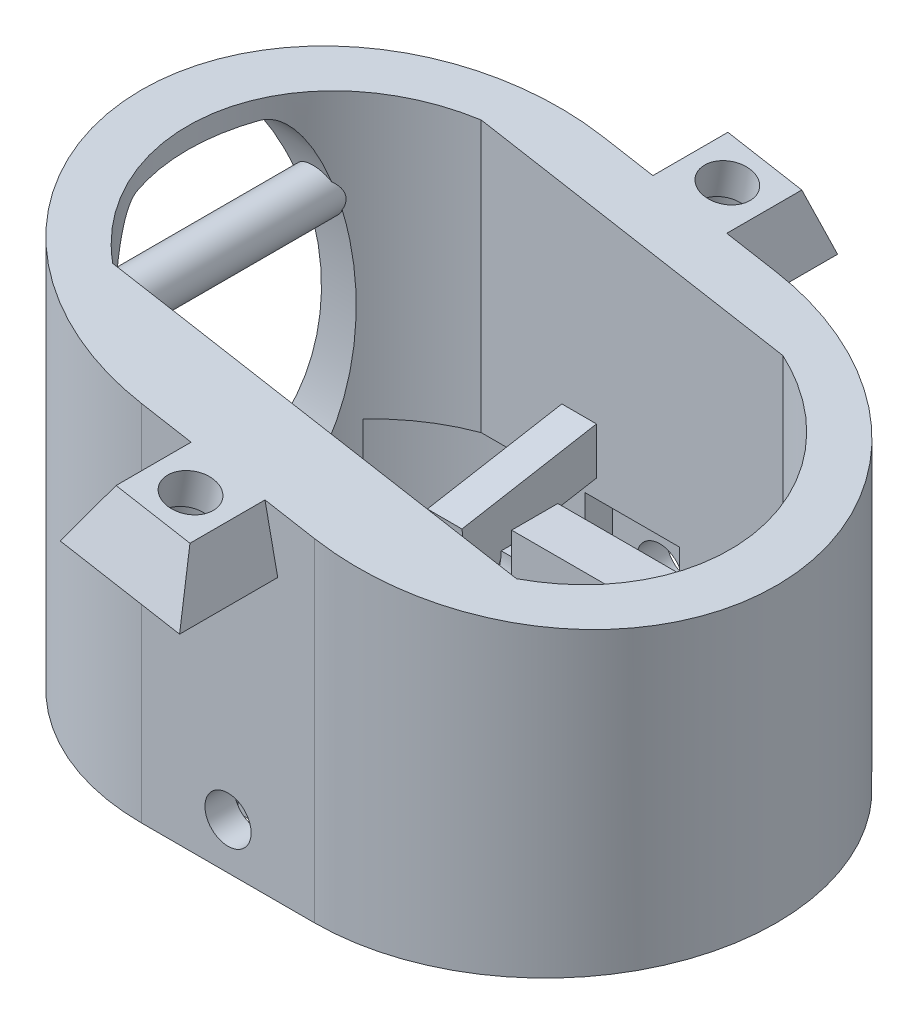
SolidWorks part; units mm, degrees
ref_plane "Front Plane" through (0, 0, 0) normal (0, 0, 1) x (1, 0, 0)
ref_plane "Top Plane" through (0, 0, 0) normal (0, 1, 0) x (1, 0, 0)
ref_plane "Right Plane" through (0, 0, 0) normal (1, 0, 0) x (0, 0, -1)
sketch "Sketch1" plane through (0, 0, 0) normal (0, 1, 0) x (1, 0, 0)
  line L0 (-7.5, 0) -> (7.5, 0) construction
  line L1 (-7.5, 20) -> (7.5, 20)
  line L2 (-7.5, -20) -> (7.5, -20)
  line L3 (22.4666, 10) -> (22.4666, -10) construction
  line L4 (22.4666, 10) -> (20.8037, 8.8889) construction
  line L5 (17.4875, -12.5) -> (-15.6093, -12.5)
  line L6 (22.4666, 10) -> (24.1296, 11.1111) construction
  line L7 (-7.5, 15) -> (13.0678, 15)
  line L8 (-7.5, 16) -> (7.5, 16) construction
  line L9 (-7.5, -16) -> (7.5, -16) construction
  line L10 (20.2481, 9.7204) -> (21.3592, 8.0574) construction
  line L11 (22.4666, -10) -> (20.8037, -8.8889) construction
  line L12 (22.4666, -10) -> (24.1296, -11.1111) construction
  line L13 (20.2481, -9.7204) -> (21.3592, -8.0574) construction
  line L14 (22.4666, 0) -> (23.5, 0) construction
  line L15 (0, 0) -> (0, -20) construction
  line L16 (-7.5, 17.1) -> (-7.5, 14.9)
  line L17 (0, -17.45) -> (4.1, -20) construction
  line L18 (-4.1, -15.05) -> (4.1, -15.05)
  line L19 (-4.1, -15.05) -> (-4.1, -17.45)
  line L20 (-7.5, -14.9) -> (-7.5, -17.1)
  line L21 (-4.1, -17.45) -> (4.1, -17.45)
  line L22 (4.1, -15.05) -> (4.1, -17.45)
  line L23 (-4.1, 17.4) -> (4.1, 17.4)
  line L24 (-4.1, 17.4) -> (-4.1, 15)
  line L25 (-4.1, 15) -> (4.1, 15)
  line L26 (4.1, 17.4) -> (4.1, 15)
  line L27 (4.1, -20) -> (4.1, -12.5) construction
  line L28 (4.1, -12.5) -> (0, -15.05) construction
  line L29 (-18.3972, 10.1618) -> (-20.0061, 11.6622)
  line L31 (-20.0061, -11.6622) -> (-18.3972, -10.1618)
  arc A0 (-7.5, 20) -> (-7.5, -20) centre (-7.5, 0) ccw
  arc A1 (7.5, -20) -> (7.5, 20) centre (7.5, 0) ccw
  arc A2 (17.4875, -12.5) -> (13.0678, 15) centre (7.5, 0) ccw
  arc A3 (-18.3972, -10.1618) -> (-7.5, -14.9) centre (-7.5, 0) ccw
  arc A4 (-7.5, 16) -> (-7.5, -16) centre (-7.5, 0) ccw construction
  arc A5 (7.5, -16) -> (7.5, 16) centre (7.5, 0) ccw construction
  circle A6 centre (22.4666, 10) radius 1.1
  circle A7 centre (22.4666, -10) radius 1.1
  arc A8 (-7.5, 17.1) -> (-20.0061, 11.6622) centre (-7.5, 0) ccw
  arc A9 (-7.5, 14.9) -> (-18.3972, 10.1618) centre (-7.5, 0) ccw
  arc A10 (-7.5, 17.1) -> (-20.0061, 11.6622) centre (-7.5, 0) ccw
  arc A11 (-20.0061, -11.6622) -> (-7.5, -17.1) centre (-7.5, 0) ccw
  arc A12 (-20.0061, -11.6622) -> (-7.5, -17.1) centre (-7.5, 0) ccw
  arc A13 (-19.2017, -10.912) -> (-19.2017, 10.912) centre (-7.5, 0) cw
  point P3 (0, 0)
  point P23 (20.8037, 8.8889)
  point P31 (20.8037, -8.8889)
  point P32 (0, -20)
  point P48 (0, -15.05)
  point P54 (4.1, -16.25)
  point P55 (4.1, -16.25)
  dimension "D7" = 2.2
  dimension "D10" = 34.2
  dimension "D11" = 29.8
  dimension "D14" = 4
  dimension "D1" = 15
  dimension "D2" = 40
  dimension "D3" = 7.5
  dimension "D4" = 5
  dimension "D6" = 20
  dimension "D8" = 8.2
  dimension "D9" = 2.4
  dimension "D12" = 137
  dimension "D13" = 137
  dimension "D5" = 4
extrude "Boss-Extrude1" add sketch "Sketch1" along normal blind 10 and the other way blind 10 contours L2 A1 L1 A0 A7 A6 L16 A9 L7 A2 L5 L18 L20 A8 region at (0, 0, -19.3199)
sketch "Sketch3" plane through (0, 10, 0) normal (0, 1, 0) x (1, 0, 0)
  line L0 (-7.5, 0) -> (7.5, 0) construction
  line L1 (-7.5, 20) -> (7.5, 20)
  line L2 (-7.5, -20) -> (7.5, -20)
  line L3 (-7.5, 20) -> (7.5, 20) construction
  line L6 (13.0678, 15) -> (-13.0678, 15)
  line L8 (17.4875, -12.5) -> (-17.4875, -12.5)
  line L11 (-7.5, 15) -> (-4.1, 15) construction
  line L12 (-7.5, 16) -> (7.5, 16) construction
  line L13 (-7.5, -16) -> (7.5, -16) construction
  arc A0 (-7.5, 20) -> (-7.5, -20) centre (-7.5, 0) ccw
  arc A1 (7.5, -20) -> (7.5, 20) centre (7.5, 0) ccw
  arc A2 (-7.5, 20) -> (-7.5, -20) centre (-7.5, 0) ccw construction
  arc A3 (17.4875, -12.5) -> (13.0678, 15) centre (7.5, 0) ccw
  arc A4 (-13.0678, 15) -> (-17.4875, -12.5) centre (-7.5, 0) ccw
  arc A5 (-7.5, 16) -> (-7.5, -16) centre (-7.5, 0) ccw construction
  arc A6 (7.5, -16) -> (7.5, 16) centre (7.5, 0) ccw construction
  point P2 (0, 0)
  dimension "D2" = 7.5
  dimension "D1" = 4
extrude "Boss-Extrude2" add sketch "Sketch3" against normal blind 11
sketch "Sketch4" plane through (0, 0, 0) normal (0, 0, 1) x (1, 0, 0)
  line L0 (-7.5, -10) -> (7.5, -10) construction
  line L1 (-4, -2) -> (4, -2) construction
  line L2 (-4, -2) -> (-4, -10) construction
  line L3 (-4, -10) -> (4, -10) construction
  line L4 (4, -2) -> (4, -10) construction
  line L5 (0, 0) -> (0, -2) construction
  line L6 (-4, -10) -> (4, -2) construction
  circle A0 centre (0, -6) radius 2
  point P11 (0, -6)
  dimension "D2" = 4
  dimension "D1" = 8
extrude "Cut-Extrude1" cut sketch "Sketch4" against normal blind 25 and the other way blind 35
sketch "Sketch5" plane through (0, 10, 0) normal (0, 1, 0) x (1, 0, 0)
  line L0 (-7.5, 0) -> (7.5, 0) construction
  line L1 (-7.5, 20) -> (7.5, 20)
  line L2 (-7.5, -20) -> (7.5, -20)
  line L3 (-7.5, 20) -> (7.5, 20) construction
  line L6 (-13.0678, 15) -> (13.0678, 15)
  line L8 (17.4875, -12.5) -> (-17.4875, -12.5)
  line L10 (-7.5, 16) -> (7.5, 16) construction
  line L11 (-7.5, -16) -> (7.5, -16) construction
  arc A0 (-7.5, 20) -> (-7.5, -20) centre (-7.5, 0) ccw
  arc A1 (7.5, -20) -> (7.5, 20) centre (7.5, 0) ccw
  arc A2 (17.4875, -12.5) -> (13.0678, 15) centre (7.5, 0) ccw
  arc A3 (-13.0678, 15) -> (-17.4875, -12.5) centre (-7.5, 0) ccw
  arc A4 (-7.5, 16) -> (-7.5, -16) centre (-7.5, 0) ccw construction
  arc A5 (7.5, -16) -> (7.5, 16) centre (7.5, 0) ccw construction
  point P2 (0, 0)
  point P22 (0, -12.5)
  dimension "D1" = 7.5
extrude "Boss-Extrude3" add sketch "Sketch5" along normal blind 15
sketch "Sketch6" plane through (0, 0, 0) normal (0, 0, 1) x (1, 0, 0)
  line L0 (-27.5, 25) -> (27.5, 15.302)
  line L1 (27.5, -10) -> (27.5, 25) construction
  line L2 (-7.5, 25) -> (-27.5, 25) construction
  line L3 (-27.5, 25) -> (27.5, 25)
  line L4 (27.5, 25) -> (27.5, 15.302)
  dimension "D1" = 10
extrude "Cut-Extrude2" cut sketch "Sketch6" against normal blind 20 and the other way blind 20
sketch "Sketch7" plane through (0, 0, 0) normal (0, 0, 1) x (1, 0, 0)
  line L0 (-27.5, 25) -> (-27.5, -10) construction
  line L1 (-27.5, -10) -> (-7.5, -10) construction
  line L2 (-22.5, 24.1184) -> (-22.5, -10) construction
  line L3 (-7.5, -10) -> (-7.5, 21.4735) construction
  line L4 (-13.0678, 22.4552) -> (-23.5, 24.2947) construction
  line L5 (-27.5, 25) -> (-27.5, -10)
  arc A0 (-26.7857, -7.5) -> (-26.7857, 22.5) centre (-50.8929, 7.5) ccw
  arc A1 (-26.7857, -7.5) -> (-27.5, -10) centre (-22.7679, -10) ccw
  arc A2 (-27.5, 25) -> (-26.7857, 22.5) centre (-22.7679, 25) ccw
  point P0 (-27.5, 25)
  dimension "D1" = 2.5
  dimension "D2" = 5
extrude "Cut-Extrude3" cut sketch "Sketch7" against normal blind 20 and the other way blind 20
sketch "Sketch8" plane through (0, 0, 0) normal (1, 0, 0) x (0, 0, -1)
  line L0 (0, 7.5) -> (0, 0) construction
  line L1 (5.2973, 22.5) -> (-5.2973, 22.5)
  line L2 (10.5946, 7.5) -> (-10.5946, 7.5) construction
  line L3 (5.2973, -7.5) -> (-5.2973, -7.5)
  ellipse E0 centre (5.2973, 7.5) end of major axis (5.2973, 22.5) minor radius 5.2973 (5.2973, -7.5) -> (5.2973, 22.5) ccw
  ellipse E1 centre (-5.2973, 7.5) end of major axis (-5.2973, 22.5) minor radius 5.2973 (-5.2973, 22.5) -> (-5.2973, -7.5) ccw
  dimension "D1" = 30
  dimension "D2" = 21.1891
extrude "Cut-Extrude4" cut sketch "Sketch8" against normal blind 40
sketch "Sketch9" plane through (0, 0, 0) normal (0, 0, 1) x (1, 0, 0)
  line L0 (-24.6917, 22.5) -> (-21.8926, 15.5419) construction
  line L1 (-26.7857, 22.5) -> (-22.5976, 22.5) construction
  line L2 (-23.5325, 15.0872) -> (-21.8926, 15.5419) construction
  line L3 (-21.8926, 15.5419) -> (-20.2527, 15.9967) construction
  line L4 (-23.9221, 16.4923) -> (-23.1428, 13.682) construction
  circle A0 centre (-21.8926, 15.5419) radius 2
  arc A2 (-26.1088, -6.3529) -> (-26.1088, 21.3529) centre (-50.8929, 7.5) ccw construction
  spline S1 degree 3 poles (-22.5976, -7.5) (-22.5373, -7.5) (-22.4754, -7.4764) (-22.3489, -7.3888) (-22.284, -7.3239) (-22.1573, -7.1668) (-22.0949, -7.0742) (-21.9716, -6.8671) (-21.9106, -6.7525) (-21.734, -6.3915) (-21.6227, -6.1255) (-21.409, -5.561) (-21.3068, -5.2623) (-21.0161, -4.3444) (-20.8408, -3.6968) (-20.5233, -2.3725) (-20.3809, -1.6929) (-20.128, -0.3198) (-20.0173, 0.3753) (-19.8265, 1.7801) (-19.7466, 2.4892) (-19.5546, 4.6227) (-19.4899, 6.0612) (-19.4897, 8.9332) (-19.5543, 10.3716) (-19.746, 12.5054) (-19.8259, 13.2147) (-20.0165, 14.6196) (-20.1273, 15.3155) (-20.3806, 16.6918) (-20.5227, 17.3698) (-20.8404, 18.6954) (-21.0153, 19.3418) (-21.3061, 20.2604) (-21.4073, 20.5561) (-21.6198, 21.1183) (-21.7314, 21.3857) (-21.9095, 21.7503) (-21.9698, 21.864) (-22.093, 22.0712) (-22.1563, 22.1655) (-22.2837, 22.3237) (-22.3472, 22.3873) (-22.474, 22.4758) (-22.5373, 22.5) (-22.5976, 22.5) knots 0 0 0 0 0.015625 0.015625 0.03125 0.03125 0.046875 0.046875 0.0625 0.0625 0.09375 0.09375 0.125 0.125 0.1875 0.1875 0.25 0.25 0.3125 0.3125 0.375 0.375 0.5 0.5 0.625 0.625 0.6875 0.6875 0.75 0.75 0.8125 0.8125 0.875 0.875 0.90625 0.90625 0.9375 0.9375 0.953125 0.953125 0.96875 0.96875 0.984375 0.984375 1 1 1 1 construction
  point P15 (-23.5325, 15.0872)
  dimension "D1" = 7.5
  dimension "D2" = 4
  dimension "D3" = 4
extrude "Boss-Extrude4" add sketch "Sketch9" along normal blind 10.2 and the other way blind 10.2
sketch "Sketch11" plane through (0, 0, 0) normal (0, 0, 1) x (1, 0, 0)
  line L0 (9.5666, 2.5) -> (6.5666, 2.5) construction
  line L1 (9.5666, 7.5) -> (23.5666, 7.5)
  line L2 (9.5666, 7.5) -> (9.5666, -2.5)
  line L3 (9.5666, -2.5) -> (23.5666, -2.5)
  line L4 (23.5666, -5) -> (23.5666, -2.5)
  line L5 (13.0678, -10) -> (23.5, -10) construction
  line L8 (6.5666, 10) -> (6.5666, -5)
  line L11 (23.5666, 10) -> (23.5666, 7.5)
  line L13 (6.5666, 10) -> (23.5666, 10)
  line L15 (6.5666, -5) -> (23.5666, -5)
  line L16 (23.5666, -10) -> (23.5666, -1) construction
  dimension "D1" = 10
  dimension "D2" = 3
  dimension "D3" = 5
  dimension "D4" = 15
  dimension "D5" = 17
extrude "Boss-Extrude6" add sketch "Sketch11" along normal blind 2 and the other way blind 2
sketch "Sketch12" plane through (6.5666, 0, 0) normal (-1, 0, 0) x (0, 0, 1)
  line L0 (0, 0) -> (0, 2) construction
  line L1 (-6, 2) -> (-4, 2)
  line L2 (4, 2) -> (6, 2)
  line L3 (-2, -5) -> (2, -5) construction
  arc A0 (-4, 2) -> (4, 2) centre (0, 2) ccw
  arc A1 (-6, 2) -> (6, 2) centre (0, 2) ccw
  point P13 (0, -4)
  dimension "D1" = 8
  dimension "D2" = 2
  dimension "D3" = 1
extrude "Boss-Extrude7" add sketch "Sketch12" along normal blind 6.9
sketch "Sketch14" plane through (0, 0, 0) normal (0, 0, 1) x (1, 0, 0)
  line L0 (-0.5334, -3) -> (-3.0834, -3)
  line L1 (-0.3334, 2) -> (-0.3334, -4) construction
  line L2 (0.3285, 2) -> (-11.1531, 2) construction
  line L3 (-0.5334, -3) -> (-0.3334, -2.8)
  line L4 (-0.3334, 2) -> (-0.3334, -2) construction
  line L5 (-3.0834, -3) -> (-3.0834, -5.5)
  line L6 (-3.0834, -5.5) -> (-0.3334, -5.5)
  line L7 (-0.3334, -5.5) -> (1.1666, -4)
  line L8 (1.1666, -4) -> (-0.3334, -4)
  line L9 (-0.3334, -4) -> (-0.3334, -2.8)
  line L10 (-0.3334, 2) -> (6.5666, 2) construction
  point P4 (-1.8084, -3)
  dimension "D1" = 1
  dimension "D2" = 0.2
  dimension "D3" = 0.2
  dimension "D4" = 2.75
  dimension "D5" = 1.5
revolve "Revolve1" add sketch "Sketch14" angle 45 about L2 other way angle 45
sketch "Sketch15" plane through (0, 0, 0) normal (0, 0, 1) x (1, 0, 0)
  line L0 (-3.0834, -1.4) -> (-3.0834, -5.5)
  line L1 (-3.0834, -3.3033) -> (-3.0834, -5.5) construction
  line L2 (-3.0834, -5.5) -> (-6.0834, -5.5)
  line L3 (-6.0834, -5.5) -> (-6.0834, -1.4)
  line L4 (-6.0834, -1.4) -> (-3.0834, -1.4)
  line L5 (-3.716, 2) -> (-11.4876, 2) construction
  line L6 (-0.3334, 2) -> (6.5666, 2) construction
  dimension "D1" = 3
  dimension "D2" = 3.4
revolve "Revolve2" add sketch "Sketch15" angle 100 about L5 other way angle 100
sketch "Sketch16" plane through (0, 1.9397, 0.342) normal (0, 0.9848, 0.1736) x (1, 0, 0)
  line L0 (-3.0834, 7.8473) -> (-3.0834, 3.7473) construction
  line L1 (-6.0834, 3.7473) -> (-3.0834, 3.7473)
  line L2 (-6.0834, 3.7473) -> (-6.0834, 18.7473)
  line L3 (-6.0834, 18.7473) -> (-3.0834, 18.7473)
  line L4 (-3.0834, 3.7473) -> (-3.0834, 18.7473)
  dimension "D1" = 15
extrude "Boss-Extrude8" add sketch "Sketch16" against normal blind 4
sketch "Sketch17" plane through (0, 1.9397, -0.342) normal (0, 0.9848, -0.1736) x (1, 0, 0)
  line L0 (-3.0834, -7.8473) -> (-3.0834, -3.7473) construction
  line L1 (-6.0834, -3.7473) -> (-3.0834, -3.7473)
  line L2 (-6.0834, -3.7473) -> (-6.0834, -14.8652)
  line L3 (-6.0834, -14.8652) -> (-3.0834, -14.8652)
  line L4 (-3.0834, -3.7473) -> (-3.0834, -14.8652)
  line L5 (-6.0834, 2.8477) -> (-6.0834, 13.9655) construction
  dimension "D1" = 11.1179
extrude "Boss-Extrude9" add sketch "Sketch17" against normal blind 4
sketch "Sketch18" plane through (3.446, 19.5434, 0) normal (0.1736, 0.9848, 0) x (0.9848, -0.1736, 0)
  line L0 (-11.1149, 20) -> (4.1165, 20) construction
  line L1 (-6.7492, 20) -> (-0.2492, 20)
  line L2 (-6.7492, 20) -> (-6.7492, 26.5)
  line L3 (-6.7492, 26.5) -> (-0.2492, 26.5)
  line L4 (-0.2492, 20) -> (-0.2492, 26.5)
  line L10 (-6.7492, 26.5) -> (-3.4992, 23.25) construction
  line L11 (-3.4992, 23.25) -> (-0.2492, 20) construction
  point P15 (-3.4992, 20)
  point P16 (-3.4992, 20)
  dimension "D1" = 6.5
ref_plane "Plane1" through (2.5778, 14.6193, 0) normal (0.1736, 0.9848, 0) x (0.9848, -0.1736, 0)
sketch "Sketch19" plane through (2.5778, 14.6193, 0) normal (0.1736, 0.9848, 0) x (-0.9848, 0.1736, 0)
  line L4 (5.6496, -20) -> (-9.1225, -20) construction
  line L9 (8.7492, -20) -> (-1.7508, -20)
  line L10 (8.7492, -20) -> (8.7492, -28.5)
  line L11 (8.7492, -28.5) -> (-1.7508, -28.5)
  line L12 (-1.7508, -20) -> (-1.7508, -28.5)
  line L16 (6.7492, -20) -> (6.7492, -26.5) construction
  line L17 (6.7492, -26.5) -> (0.2492, -26.5) construction
  line L18 (0.2492, -20) -> (0.2492, -26.5) construction
  dimension "D1" = 2
  dimension "D2" = 2
  dimension "D3" = 2
loft "Loft2" add profiles "Sketch18", "Sketch19" connector at (3.2006, 19.5867, -26.5) connector at (4.302, 14.3153, -28.5)
sketch "Sketch20" plane through (3.446, 19.5434, 0) normal (0.1736, 0.9848, 0) x (0.9848, -0.1736, 0)
  line L0 (-6.7492, 26.5) -> (-3.4992, 23.25) construction
  line L1 (-3.4992, 23.25) -> (-0.2492, 20) construction
  circle A0 centre (-3.4992, 23.25) radius 2
  dimension "D1" = 4
extrude "Cut-Extrude5" cut sketch "Sketch20" against normal blind 5
sketch "Sketch22" plane through (2.5778, 14.6193, 0) normal (-0.1736, -0.9848, 0) x (0.9848, -0.1736, 0)
  circle A0 centre (-3.4992, -23.25) radius 3.25
  dimension "D1" = 6.5
extrude "Cut-Extrude6" cut sketch "Sketch22" against normal blind 2
mirror "Mirror1" about plane through (0, 0, 0) normal (0, 0, 1) of "Cut-Extrude6", "Loft2", "Cut-Extrude5"
